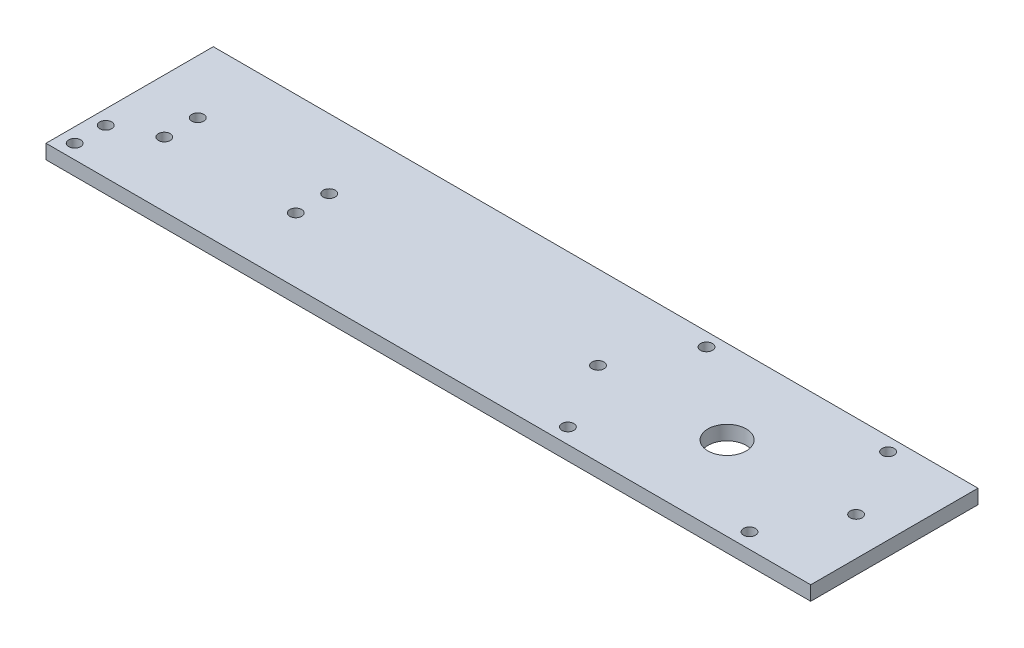
SolidWorks part; units mm, degrees
ref_plane "Front Plane" through (0, 0, 0) normal (0, 0, 1) x (1, 0, 0)
ref_plane "Top Plane" through (0, 0, 0) normal (0, 1, 0) x (1, 0, 0)
ref_plane "Right Plane" through (0, 0, 0) normal (1, 0, 0) x (0, 0, -1)
sketch "Sketch1" plane through (0, 0, 0) normal (0, 1, 0) x (1, 0, 0)
  line L0 (25, 13.2344) -> (25, -3.2344) construction
  line L1 (-100, 22.5) -> (60, 22.5)
  line L2 (-100, 22.5) -> (-100, -12.5)
  line L3 (-100, -12.5) -> (60, -12.5)
  line L4 (60, 22.5) -> (60, -12.5)
  line L5 (25, -1) -> (25, 11) construction
  line L6 (-10, -1) -> (60, -1)
  line L7 (-10, -1) -> (-10, 11)
  line L8 (-10, 11) -> (60, 11)
  line L9 (60, -1) -> (60, 11)
  line L10 (-10, -1) -> (60, 11) construction
  line L11 (-10, 11) -> (60, -1) construction
  line L12 (-75, -6.9483) -> (-75, 13.2344) construction
  line L13 (-61.25, 1) -> (-75, 1) construction
  line L14 (-75, 1) -> (-88.75, 1) construction
  circle A4 centre (25, 5) radius 4
  circle A5 centre (52, 5) radius 1.25
  circle A6 centre (-2, 5) radius 1.25
  circle A7 centre (-97, -9.5) radius 1.25
  circle A8 centre (-97, -3) radius 1.25
  circle A9 centre (-88.75, 8) radius 1.25
  circle A10 centre (-61.25, 8) radius 1.25
  circle A11 centre (-61.25, 1) radius 1.25
  circle A12 centre (-88.75, 1) radius 1.25
  point P0 (0, 0)
  dimension "D3" = 2.5
  dimension "D4" = 35
  dimension "D5" = 2.5
  dimension "D9" = 2.5
  dimension "D13" = 2.5
  dimension "D2" = 8
  dimension "D19" = 125
  dimension "D21" = 6
  dimension "D22" = 6
  dimension "D23" = 100
  dimension "D15" = 7
  dimension "D1" = 35
  dimension "D6" = 8
  dimension "D7" = 70
  dimension "D8" = 12
  dimension "D10" = 3
  dimension "D11" = 6.5
  dimension "D12" = 3
  dimension "D14" = 14.5
  dimension "D18" = 27.5
  dimension "D20" = 11.5
  dimension "D16" = 2
  dimension "D17" = 2
extrude "Boss-Extrude1" add sketch "Sketch1" along normal blind 3 contours L7 L8 L4 L1 L2 L3 L6 | L8 L7 L6 L4 A4 A5 A6 region at (-27.6025, 0, -5.0254) region at (59.2898, 0, -5)
sketch "Sketch2" plane through (0, 0, 0) normal (0, 0, 1) x (1, 0, 0)
  line L0 (-94.5, 33) -> (-94.5, -17) construction
  line L1 (-92, 33) -> (-92, -17)
  line L2 (-97, 33) -> (-97, -17)
  line L3 (-89, 33) -> (-89, -17)
  line L4 (-100, 33) -> (-100, -17)
  line L5 (-100, 3) -> (-100, 0) construction
  line L7 (-94, 6.4998) -> (-61.5, 6.4998)
  line L8 (-94, 6.4998) -> (-94, -3.3981)
  line L9 (-94, -3.3981) -> (-61.5, -3.3981)
  line L10 (-61.5, 6.4998) -> (-61.5, -3.3981)
  arc A0 (-92, 33) -> (-97, 33) centre (-94.5, 33) ccw
  arc A1 (-97, -17) -> (-92, -17) centre (-94.5, -17) ccw
  arc A2 (-100, -17) -> (-89, -17) centre (-94.5, -17) ccw
  arc A3 (-89, 33) -> (-100, 33) centre (-94.5, 33) ccw
  point P2 (-94.5, 8)
  dimension "D4" = 5.5
  dimension "D1" = 3
  dimension "D2" = 3
  dimension "D3" = 5
  dimension "D5" = 50
  dimension "D6" = 50
  dimension "D7" = 6
  dimension "D8" = 32.5
extrude "Cut-Extrude3" [suppressed] cut sketch "Sketch2" along normal up to surface (9 mm away) from offset 3.5 contours L1 L9 L3 L7 | L10 L7 L3 L9 | L8 L9 L1 L7
ref_plane "Plane3" through (0, 3, 0) normal (0, -1, 0) x (-1, 0, 0)
sketch "Sketch3" plane through (0, 3, 0) normal (0, -1, 0) x (-1, 0, 0)
  line L0 (-60, -12.5) -> (2, -12.5)
  line L2 (2, 5) -> (2, -12.5) construction
  line L3 (-52, 5) -> (-52, -12.5) construction
  line L5 (-47.0043, 22.7064) -> (-47.0043, -12.2936)
  line L6 (-37.5, -12.5) -> (25.1934, -12.5) construction
  line L7 (2, -12.5) -> (2, 22.5)
  line L8 (100, 22.5) -> (-60, 22.5) construction
  line L9 (2, 22.5) -> (-60, 22.5)
  line L10 (-3, 22.5) -> (-3, -12.5)
  line L11 (-47.0043, 22.7064) -> (-3, 22.5)
  line L12 (-47.0043, -12.2936) -> (-3, -12.5)
  circle A4 centre (-44, -9.3076) radius 1.25
  circle A5 centre (-6, -9.3076) radius 1.25
  circle A6 centre (-6, 19.6924) radius 1.25
  circle A7 centre (-44, 19.6924) radius 1.25
  point P14 (-47.0043, 5.2064)
  dimension "D3" = 35
  dimension "D4" = 5
  dimension "D8" = 8
  dimension "D14" = 2.5
  dimension "D1" = 54
  dimension "D2" = 5
  dimension "D5" = 62
  dimension "D6" = 54
  dimension "D7" = 44.0043
  dimension "D9" = 3.0043
  dimension "D10" = 3
  dimension "D13" = 3
  dimension "D11" = 2
  dimension "D12" = 2
extrude "Cut-Extrude7" cut sketch "Sketch3" along normal blind 10 contours A4 | A7 | A6 | A5 region at (44, 3, 9.3076)
